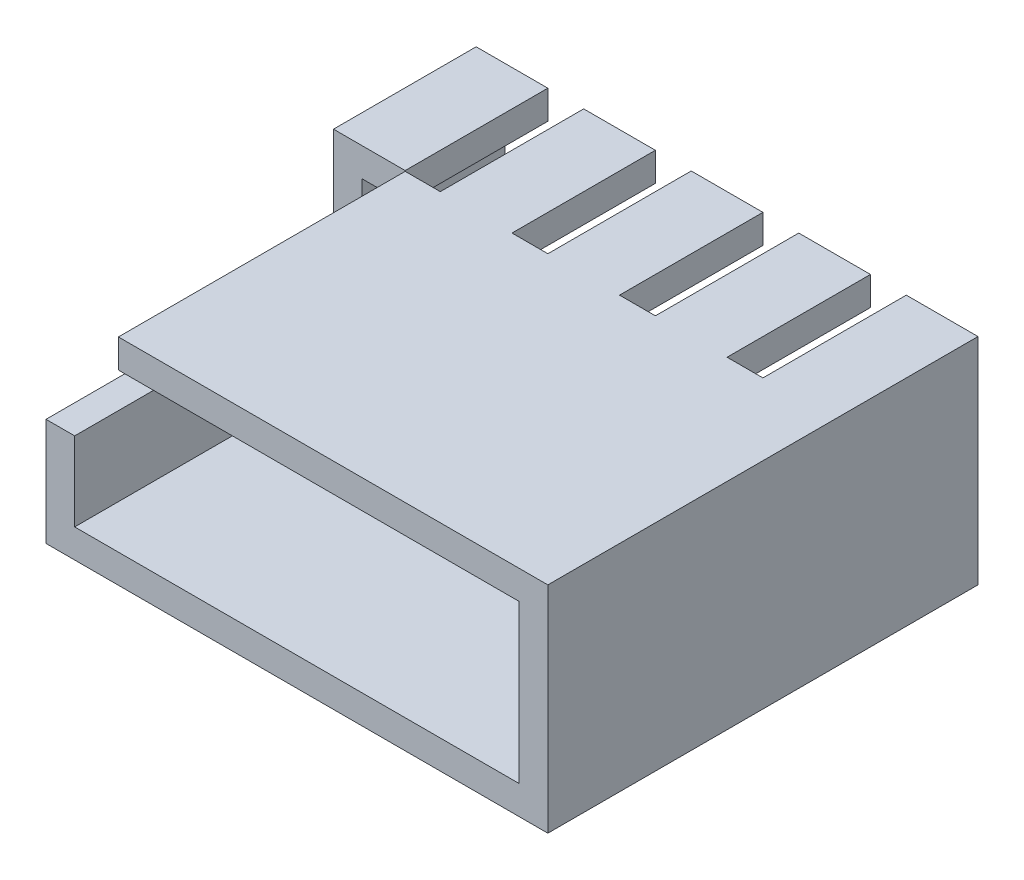
SolidWorks part; units mm, degrees
ref_plane "Front Plane" through (0, 0, 0) normal (0, 0, 1) x (1, 0, 0)
ref_plane "Top Plane" through (0, 0, 0) normal (0, 1, 0) x (1, 0, 0)
ref_plane "Right Plane" through (0, 0, 0) normal (1, 0, 0) x (0, 0, -1)
sketch "Sketch1" plane through (0, 0, 0) normal (0, 1, 0) x (1, 0, 0)
  line L1 (0, 0) -> (88.9, 0)
  line L2 (0, 0) -> (0, 76.2)
  line L3 (0, 76.2) -> (88.9, 76.2)
  line L4 (88.9, 0) -> (88.9, 76.2)
  dimension "D1" = 76.2
  dimension "D2" = 88.9
extrude "Boss-Extrude1" add sketch "Sketch1" along normal blind 38.1 contours L1 L4 L3 L2
shell "Shell1" thickness 5.08 removed face at (44.45, 19.05, -76.2) removed face at (44.45, 19.05, 0)
sketch "Sketch4" plane through (0, 0, 0) normal (0, -1, 0) x (1, 0, 0)
  line L1 (0, 0) -> (12.827, 0)
  line L2 (0, 0) -> (0, -50.927)
  line L3 (0, -50.927) -> (12.827, -50.927)
  line L4 (12.827, 0) -> (12.827, -50.927)
  dimension "D1" = 50.927
  dimension "D2" = 12.827
extrude "Cut-Extrude3" cut sketch "Sketch4" against normal through all from offset 19.05 offset against normal yes
sketch "Sketch5" plane through (0, 38.1, 0) normal (0, 1, 0) x (1, 0, 0)
  line L0 (0, 76.2) -> (88.9, 76.2) construction
  line L1 (12.7, 76.2) -> (19.05, 76.2)
  line L2 (12.7, 76.2) -> (12.7, 50.8)
  line L3 (12.7, 50.8) -> (19.05, 50.8)
  line L4 (19.05, 76.2) -> (19.05, 50.8)
  line L5 (31.75, 76.2) -> (31.75, 50.8)
  line L6 (31.75, 76.2) -> (38.1, 76.2)
  line L7 (38.1, 76.2) -> (38.1, 50.8)
  line L8 (31.75, 50.8) -> (38.1, 50.8)
  line L9 (50.8, 76.2) -> (50.8, 50.8)
  line L10 (50.8, 76.2) -> (57.15, 76.2)
  line L11 (57.15, 76.2) -> (57.15, 50.8)
  line L12 (50.8, 50.8) -> (57.15, 50.8)
  line L13 (69.85, 76.2) -> (69.85, 50.8)
  line L14 (69.85, 76.2) -> (76.2, 76.2)
  line L15 (76.2, 76.2) -> (76.2, 50.8)
  line L16 (69.85, 50.8) -> (76.2, 50.8)
  line L17 (12.7, 63.5) -> (76.2, 63.5) construction
  line L19 (12.7, 76.2) -> (5.08, 76.2) construction
  line L20 (0, 50.927) -> (0, 76.2) construction
  line L21 (76.2, 76.2) -> (83.82, 76.2) construction
  line L22 (88.9, 0) -> (88.9, 76.2) construction
  dimension "D1" = 25.4
  dimension "D2" = 6.35
  dimension "D4" = 5.08
  dimension "D5" = 5.08
  dimension "D6" = 63.5
  dimension "D3" = 4
extrude "Cut-Extrude4" cut sketch "Sketch5" against normal through all
